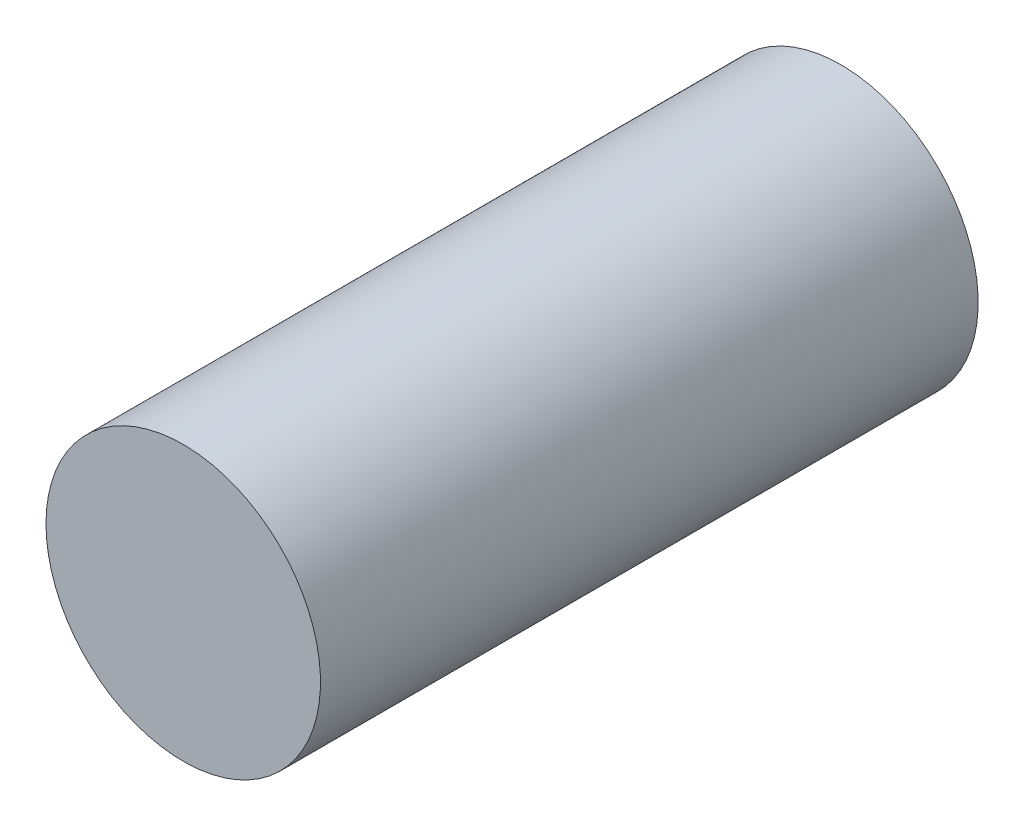
SolidWorks part; units mm, degrees
material "Alloy Steel"
ref_plane "Front Plane" through (0, 0, 0) normal (0, 0, 1) x (1, 0, 0)
ref_plane "Top Plane" through (0, 0, 0) normal (0, 1, 0) x (1, 0, 0)
ref_plane "Right Plane" through (0, 0, 0) normal (1, 0, 0) x (0, 0, -1)
sketch "Sketch1" plane through (0, 0, 0) normal (0, 0, 1) x (1, 0, 0)
  circle A0 centre (0, 0) radius 31.8021
  dimension "D1" = 63.6041
extrude "Extrude1" add sketch "Sketch1" along normal mid plane 152.4
ref_axis "Axis1" through (0, 0, 76.2) along (0, 0, -1)
